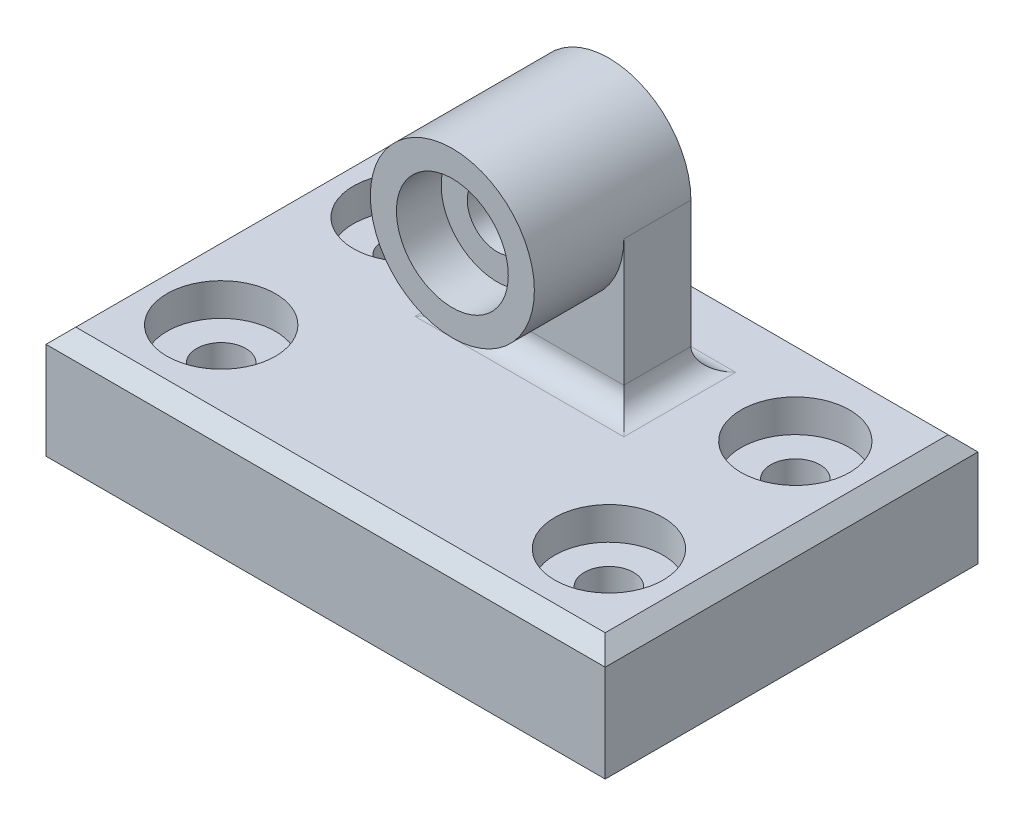
SolidWorks part; units mm, degrees
material "Brass"
ref_plane "Front Plane" through (0, 0, 0) normal (0, 0, 1) x (1, 0, 0)
ref_plane "Top Plane" through (0, 0, 0) normal (0, 1, 0) x (1, 0, 0)
ref_plane "Right Plane" through (0, 0, 0) normal (1, 0, 0) x (0, 0, -1)
sketch "Sketch1" plane through (0, 0, 0) normal (0, 1, 0) x (1, 0, 0)
  line L1 (-37.5, 25) -> (37.5, 25)
  line L2 (-37.5, 25) -> (-37.5, -25)
  line L3 (-37.5, -25) -> (37.5, -25)
  line L4 (37.5, 25) -> (37.5, -25)
  line L5 (-37.5, 25) -> (37.5, -25) construction
  line L6 (-37.5, -25) -> (37.5, 25) construction
  point P0 (0, 0)
  dimension "D1" = 75
  dimension "D2" = 50
extrude "BASE" add sketch "Sketch1" along normal blind 15
sketch "Sketch3" plane through (0, 0, 0) normal (0, 1, 0) x (1, 0, 0)
  line L0 (37.5, 25) -> (-37.5, 25) construction
  line L1 (-11, 4) -> (11, 4)
  line L2 (-11, 4) -> (-11, 13)
  line L3 (-11, 13) -> (11, 13)
  line L4 (11, 4) -> (11, 13)
  dimension "D1" = 9
  dimension "D2" = 22
  dimension "D3" = 11
  dimension "D4" = 12
extrude "PILLAR" add sketch "Sketch3" along normal blind 35
sketch "Sketch4" plane through (0, 0, -13) normal (0, 0, -1) x (-1, 0, 0)
  line L0 (11, 35) -> (-11, 35) construction
  circle A0 centre (0, 35) radius 11
  dimension "D1" = 22
extrude "BOSS" add sketch "Sketch4" against normal blind 21
sketch "Sketch5" plane through (0, 0, 8) normal (0, 0, 1) x (1, 0, 0)
  circle A0 centre (0, 35) radius 4
  dimension "D1" = 8
extrude "BOSS_HOLE" cut sketch "Sketch5" against normal up to next
sketch "Sketch6" plane through (0, 0, 8) normal (0, 0, 1) x (1, 0, 0)
  circle A0 centre (0, 35) radius 7.5
  dimension "D1" = 15
extrude "BOSS_CounterSink" cut sketch "Sketch6" against normal blind 6
hole_wizard "CBORE for M6 Hex Head Bolt1" positions "Sketch7" profile "Sketch8" counterbore size "M6" standard "ANSI Metric" end condition up to next
sketch "Sketch7" plane through (0, 15, 0) normal (0, 1, 0) x (1, 0, 0)
  line L0 (37.5, 25) -> (-37.5, 25) construction
  point P0 (-26, -13)
  dimension "D1" = 38
  dimension "D4" = 26
sketch "Sketch8" plane through (-26, 15, 13) normal (1, 0, 0) x (0, 0, 1)
  line L0 (0, 0) -> (0, 15)
  line L1 (0, 15) -> (3.3, 15)
  line L3 (3.3, 15) -> (3.3, 4.38)
  line L4 (3.3, 4.38) -> (7.275, 4.38)
  line L5 (7.275, 4.38) -> (7.275, 0)
  line L7 (7.275, 0) -> (0, 0)
  line L11 (0, -6.35) -> (0, 107.95) construction
  dimension "Thru Hole Dia." = 6.6
  dimension "Thru Hole Depth" = 15
  dimension "C'Bore Dia." = 14.55
  dimension "C'Bore Depth" = 4.38
chamfer "Chamfer1" distance 2 angle 45 4 edges at (0, 15, 25) (0, 15, -25) (-37.5, 15, 0) (37.5, 15, 0)
fillet "Fillet2" radius 3 4 edges at (-11, 15, -8.5) (0, 15, -13) (11, 15, -8.5) (0, 15, -4)
pattern_linear "LPattern1" count 2 spacing 52 along (1, 0, 0) count 2 spacing 25 along (0, 0, -1) of "CBORE for M6 Hex Head Bolt1"
